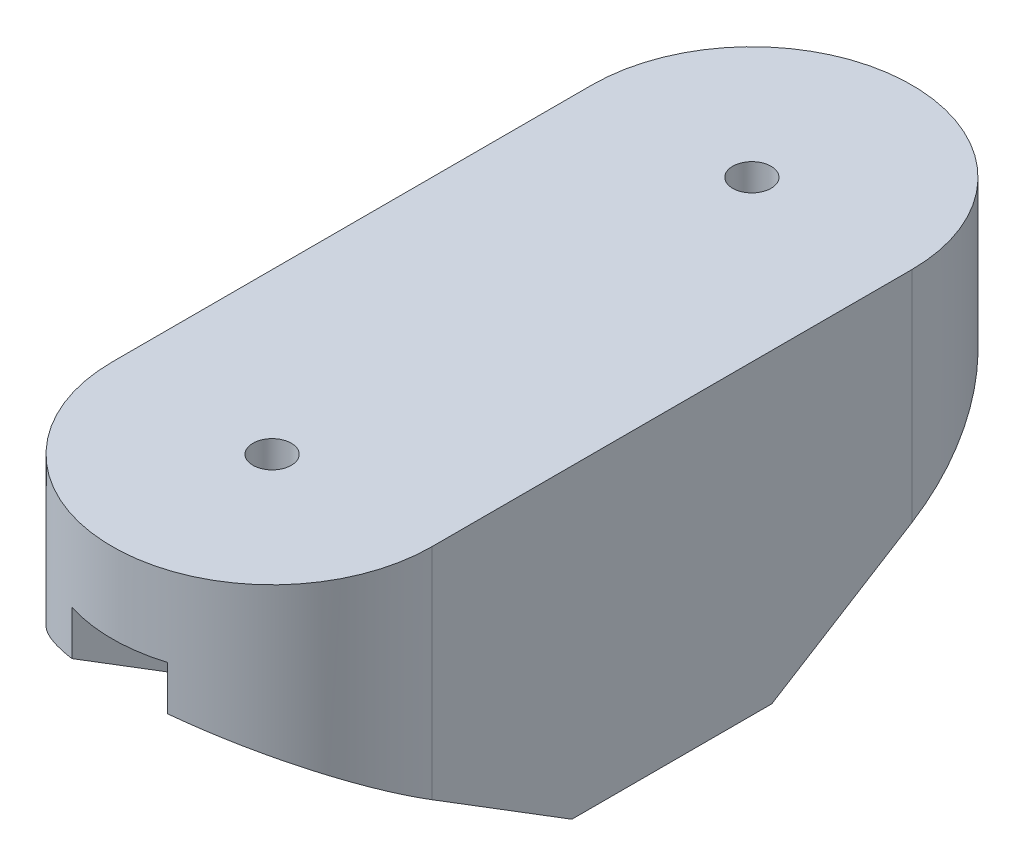
SolidWorks part; units mm, degrees
ref_plane "Front Plane" through (0, 0, 0) normal (0, 0, 1) x (1, 0, 0)
ref_plane "Top Plane" through (0, 0, 0) normal (0, 1, 0) x (1, 0, 0)
ref_plane "Right Plane" through (0, 0, 0) normal (1, 0, 0) x (0, 0, -1)
sketch "Sketch1" plane through (0, 0, 0) normal (0, 1, 0) x (1, 0, 0)
  line L0 (0, 0) -> (0, -38.1) construction
  line L1 (12.7, 0) -> (12.7, -38.1)
  line L2 (-12.7, 0) -> (-12.7, -38.1)
  line L3 (0, -35.5951) -> (-2.1693, -36.8476) construction
  line L4 (-2.1693, -36.8476) -> (-2.1693, -39.3524) construction
  line L5 (-2.1693, -39.3524) -> (0, -40.6049) construction
  line L6 (0, -40.6049) -> (2.1693, -39.3524) construction
  line L7 (2.1693, -39.3524) -> (2.1693, -36.8476) construction
  line L8 (2.1693, -36.8476) -> (0, -35.5951) construction
  line L9 (0, 3.0794) -> (-2.1693, 1.8269) construction
  line L10 (-2.1693, 1.8269) -> (-2.1693, -0.678) construction
  line L11 (-2.1693, -0.678) -> (0, -1.9304) construction
  line L12 (0, -1.9304) -> (2.1693, -0.678) construction
  line L13 (2.1693, -0.678) -> (2.1693, 1.8269) construction
  line L14 (2.1693, 1.8269) -> (0, 3.0794) construction
  arc A0 (12.7, 0) -> (-12.7, 0) centre (0, 0) ccw
  arc A1 (-12.7, -38.1) -> (12.7, -38.1) centre (0, -38.1) ccw
  circle A2 centre (0, -38.1) radius 2.1693 construction
  circle A3 centre (0, 0.5745) radius 2.1693 construction
  circle A4 centre (0, -38.1) radius 1.524 construction
  circle A5 centre (0, 0.5745) radius 1.524 construction
  point P3 (0, -19.05)
extrude "Boss-Extrude1" add sketch "Sketch1" against normal blind 6.35
sketch "Sketch2" plane through (0, 0, 0) normal (1, 0, 0) x (0, 0, -1)
  line L0 (-19.05, -6.35) -> (-19.05, -31.75) construction
  line L1 (12.7, -6.35) -> (-50.8, -6.35) construction
  line L2 (12.7, -6.35) -> (12.7, -12.7) construction
  line L3 (12.7, -12.7) -> (-11.1189, -37.0247) construction
  line L4 (-11.1189, -37.0247) -> (-26.9938, -37.0056) construction
  line L5 (-26.9938, -37.0056) -> (-50.8, -12.7) construction
  line L6 (-50.8, -12.7) -> (-50.8, -6.35) construction
  line L7 (-50.8, -6.35) -> (12.7, -6.35)
  line L8 (12.7, -6.35) -> (12.7, -9.525)
  line L9 (-19.05, -6.35) -> (-19.05, -9.525) construction
  line L10 (-11.1188, -24.3056) -> (-26.9938, -24.3056)
  line L11 (12.7, -9.525) -> (-11.1188, -24.3056)
  line L12 (-50.8, -6.35) -> (-50.8, -9.525)
  line L13 (-50.8, -9.525) -> (-26.9938, -24.3056)
  circle A0 centre (-19.05, -31.75) radius 9.525 construction
  circle A1 centre (-19.05, -19.05) radius 9.525 construction
extrude "Boss-Extrude3" add sketch "Sketch2" along normal through all and the other way through all
sketch "Sketch10" plane through (0, -6.35, 0) normal (0, 1, 0) x (1, 0, 0)
  line L0 (0, 0) -> (0, -38.1) construction
  line L1 (12.7, 0) -> (12.7, -38.1)
  line L2 (-12.7, 0) -> (-12.7, -38.1)
  line L3 (-12.7, 0) -> (12.7, -38.1) construction
  line L4 (12.7, -38.1) -> (0, -19.05) construction
  line L6 (-12.7, -50.8) -> (12.7, -50.8)
  line L7 (-12.7, -50.8) -> (-12.7, 12.7)
  line L8 (-12.7, 12.7) -> (12.7, 12.7)
  line L9 (12.7, -50.8) -> (12.7, 12.7)
  line L10 (-12.7, -50.8) -> (12.7, 12.7) construction
  line L11 (-12.7, 12.7) -> (12.7, -50.8) construction
  arc A0 (12.7, 0) -> (-12.7, 0) centre (0, 0) ccw
  arc A1 (-12.7, -38.1) -> (12.7, -38.1) centre (0, -38.1) ccw
  arc A2 (-12.7, -38.1) -> (12.7, -38.1) centre (0, -38.1) ccw construction
  arc A3 (0, -50.8) -> (12.7, -38.1) centre (0, -38.1) ccw construction
  point P2 (0, -19.05)
  arc M1 (0, 12.7) -> (12.7, 0) centre (0, 0) cw
  line M2 (12.7, 0) -> (12.7, 12.7)
  line M17 (12.7, 12.7) -> (0, 12.7)
sketch "Sketch11" plane through (0, 0, 0) normal (0, 0, 1) x (1, 0, 0)
  line L0 (0, 0) -> (0, -6.35) construction
  line L2 (12.7, -6.35) -> (0, -6.35) construction
  line L3 (-3.7847, -35.5514) -> (3.81, -35.5514)
  line L4 (-3.7847, -35.5514) -> (-3.7847, -6.35)
  line L5 (-3.7847, -6.35) -> (3.81, -6.35)
  line L6 (3.81, -35.5514) -> (3.81, -6.35)
  line L7 (-3.7847, -35.5514) -> (3.81, -6.35) construction
  line L8 (-3.7847, -6.35) -> (3.81, -35.5514) construction
  point P2 (0.0126, -20.9507)
extrude "Cut-Extrude13" cut sketch "Sketch11" against normal through all and the other way through all
extrude "Cut-Extrude19" cut sketch "Sketch10" against normal through all contours A0 L8 L7 | M17 M1 M2 | A1 L7 L6 | A1 L6 L9 region at (9.8632, -6.35, -9.8632) region at (9.8632, -6.35, 47.9632) region at (-9.8632, -6.35, -9.8632) region at (-9.8632, -6.35, 47.9632)
sketch "Sketch16" plane through (0, -6.35, 0) normal (0, -1, 0) x (1, 0, 0)
  line L0 (0, 2.5049) -> (-2.1693, 1.2524)
  line L1 (-2.1693, 1.2524) -> (-2.1693, -1.2524)
  line L2 (-2.1693, -1.2524) -> (0, -2.5049)
  line L3 (0, -2.5049) -> (2.1693, -1.2524)
  line L4 (2.1693, -1.2524) -> (2.1693, 1.2524)
  line L5 (2.1693, 1.2524) -> (0, 2.5049)
  line L6 (0, 40.4932) -> (-2.1693, 39.2407)
  line L7 (-2.1693, 39.2407) -> (-2.1693, 36.7358)
  line L8 (-2.1693, 36.7358) -> (0, 35.4834)
  line L9 (0, 35.4834) -> (2.1693, 36.7358)
  line L10 (2.1693, 36.7358) -> (2.1693, 39.2407)
  line L11 (2.1693, 39.2407) -> (0, 40.4932)
  line L12 (-12.7, 19.05) -> (12.7, 19.05) construction
  line L13 (-12.7, 0) -> (-12.7, 38.1) construction
  line L14 (12.7, 38.1) -> (12.7, 0) construction
  line L16 (0, 0) -> (0, 38.1) construction
  circle A0 centre (0, 0) radius 2.1693 construction
  circle A1 centre (0, 37.9883) radius 2.1693 construction
  circle A2 centre (0, 0) radius 1.524 construction
  circle A3 centre (0, 37.9883) radius 1.524 construction
extrude "Cut-Extrude20" cut sketch "Sketch16" against normal blind 1.778
sketch "Sketch17" plane through (0, -4.572, 0) normal (0, -1, 0) x (1, 0, 0)
  line L1 (-12.7, 19.05) -> (12.7, 19.05) construction
  line L2 (-12.7, 0) -> (-12.7, 38.1) construction
  line L3 (12.7, 38.1) -> (12.7, 0) construction
  line L4 (0, 0) -> (0, 38.1) construction
  circle A0 centre (0, 38.1) radius 1.524
  circle A1 centre (0, 0) radius 1.524
extrude "Cut-Extrude21" cut sketch "Sketch17" against normal through all
